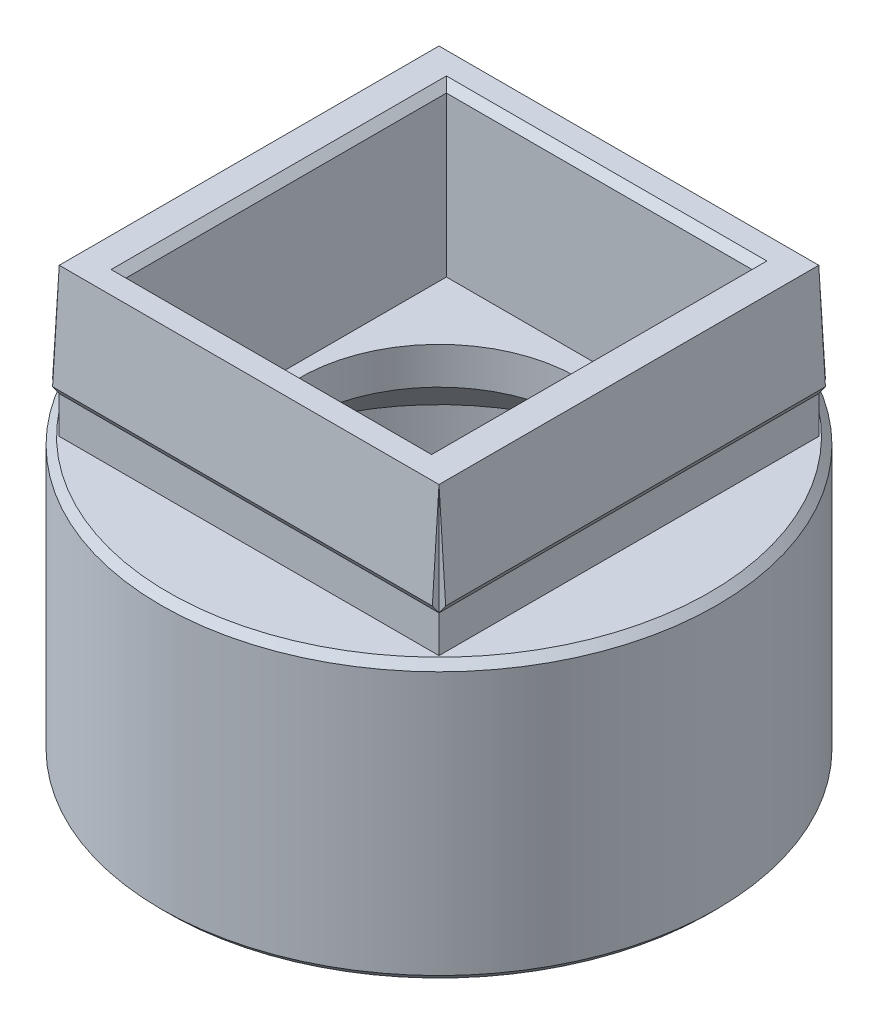
SolidWorks part; units mm, degrees
ref_plane "Alzado" through (0, 0, 0) normal (0, 0, 1) x (1, 0, 0)
ref_plane "Planta" through (0, 0, 0) normal (0, 1, 0) x (1, 0, 0)
ref_plane "Vista lateral" through (0, 0, 0) normal (1, 0, 0) x (0, 0, -1)
sketch "Croquis1" plane through (0, 0, 0) normal (0, 1, 0) x (1, 0, 0)
  line L1 (-5.125, -5.125) -> (5.125, -5.125)
  line L2 (-5.125, -5.125) -> (-5.125, 5.125)
  line L3 (-5.125, 5.125) -> (5.125, 5.125)
  line L4 (5.125, -5.125) -> (5.125, 5.125)
  line L5 (-5.125, -5.125) -> (5.125, 5.125) construction
  line L6 (-5.125, 5.125) -> (5.125, -5.125) construction
  line L7 (-4.125, -4.325) -> (4.125, -4.325)
  line L8 (-4.125, -4.325) -> (-4.125, 4.325)
  line L9 (-4.125, 4.325) -> (4.125, 4.325)
  line L10 (4.125, -4.325) -> (4.125, 4.325)
  line L11 (-4.125, -4.325) -> (4.125, 4.325) construction
  line L12 (-4.125, 4.325) -> (4.125, -4.325) construction
  point P0 (0, 0)
  point P6 (0, 0)
  dimension "D1" = 10.25
  dimension "D2" = 10.25
  dimension "D3" = 0.8
  dimension "D4" = 1
extrude "Saliente-Extruir1" add sketch "Croquis1" along normal blind 4
ref_axis "Eje1" through (0, 3.15, 0) along (0, -1, 0)
sketch "Croquis2" plane through (5.125, 0, 0) normal (1, 0, 0) x (0, 0, -1)
  line L0 (-5.125, 4) -> (-5.305, 1.25)
  line L1 (-5.305, 1.25) -> (-5.125, 1)
  line L2 (-5.125, 4) -> (-5.125, 0) construction
  line L3 (-5.125, 1) -> (-5.125, 4)
  dimension "D1" = 1
  dimension "D2" = 2.75
  dimension "D3" = 0.18
extrude "Saliente-Extruir2" add sketch "Croquis2" against normal blind 10.25
pattern_circular "MatrizC1" count 4 over 360 about axis through (0, 3.15, 0) along (0, -1, 0) of "Saliente-Extruir2"
sketch "Croquis3" plane through (0, 0, 0) normal (0, -1, 0) x (1, 0, 0)
  line L1 (4.125, 4.325) -> (-4.125, 4.325)
  line L2 (4.125, 4.325) -> (4.125, -4.325)
  line L3 (4.125, -4.325) -> (-4.125, -4.325)
  line L4 (-4.125, 4.325) -> (-4.125, -4.325)
  circle A0 centre (0, 0) radius 7.5
  dimension "D1" = 15
extrude "Saliente-Extruir3" add sketch "Croquis3" along normal blind 1
sketch "Croquis5" plane through (0, -1, 0) normal (0, -1, 0) x (1, 0, 0)
  circle A0 centre (0, 0) radius 7.5
  circle A1 centre (0, 0) radius 6
  dimension "D1" = 15
  dimension "D2" = 12
extrude "Saliente-Extruir4" add sketch "Croquis5" along normal blind 6.5
chamfer "Chaflán2" distance 0.2 angle 45 6 edges at (-4.125, 4, 0) (0, 4, 4.325) (4.125, 4, 0) (0, 4, -4.325) (0, 0, -7.5) (0, -7.5, -7.5)
chamfer "Chaflán3" distance 1 angle 45 1 edges at (0, -7.5, -6)
sketch "Croquis6" plane through (0, 4, 0) normal (0, 1, 0) x (1, 0, 0)
  circle A1 centre (0, 0) radius 3.75
  circle A3 centre (0, 0) radius 6
  circle A4 centre (0, 0) radius 6 construction
  dimension "D1" = 7.5
extrude "Saliente-Extruir5" add sketch "Croquis6" against normal blind 1 from offset 4.5 offset against normal yes
chamfer "Chaflán4" distance 2 angle 45 1 edges at (0, -1.5, 6)
